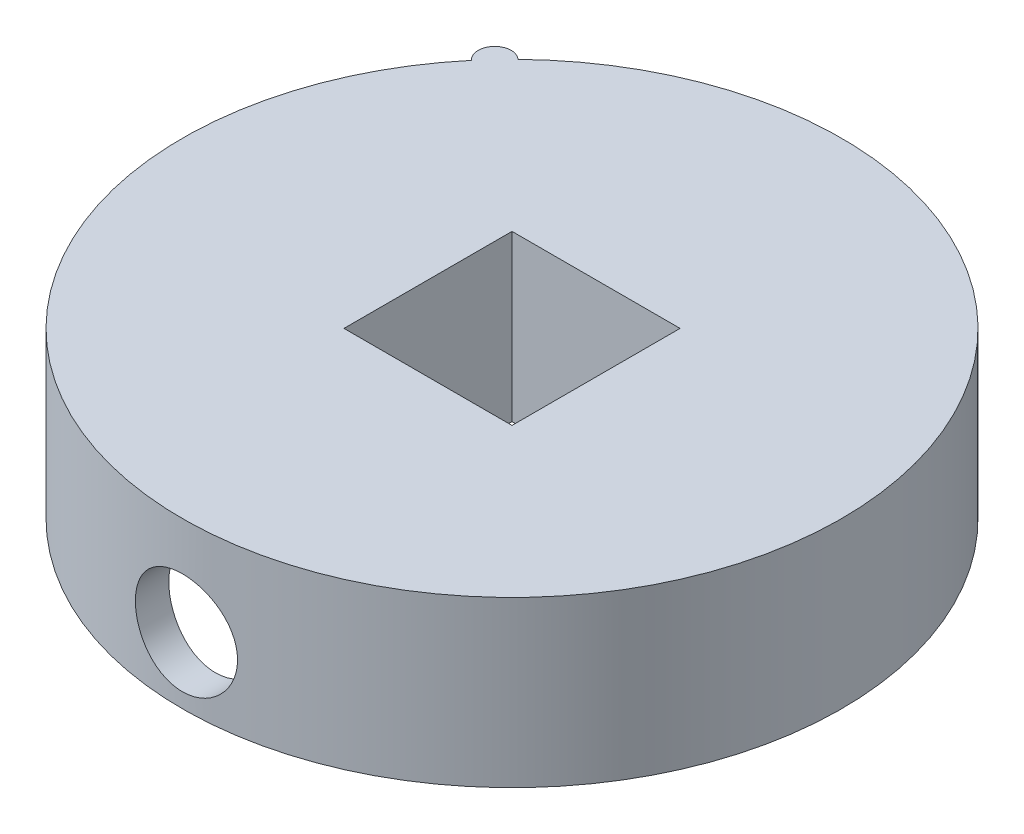
SolidWorks part; units mm, degrees
ref_plane "Спереди" through (0, 0, 0) normal (0, 0, 1) x (1, 0, 0)
ref_plane "Сверху" through (0, 0, 0) normal (0, 1, 0) x (1, 0, 0)
ref_plane "Справа" through (0, 0, 0) normal (1, 0, 0) x (0, 0, -1)
sketch "Sketch1" plane through (0, 0, 0) normal (0, 1, 0) x (1, 0, 0)
  circle A0 centre (0, 0) radius 20
  dimension "D1" = 40
extrude "Boss-Extrude1" add sketch "Sketch1" along normal blind 10
sketch "Sketch2" plane through (0, 0, 0) normal (0, -1, 0) x (1, 0, 0)
  line L1 (5.1, 5.1) -> (-5.1, 5.1)
  line L2 (5.1, 5.1) -> (5.1, -5.1)
  line L3 (5.1, -5.1) -> (-5.1, -5.1)
  line L4 (-5.1, 5.1) -> (-5.1, -5.1)
  line L5 (5.1, 5.1) -> (-5.1, -5.1) construction
  line L6 (5.1, -5.1) -> (-5.1, 5.1) construction
  point P0 (0, 0)
  dimension "D1" = 10.2
extrude "Cut-Extrude2" cut sketch "Sketch2" against normal through all
shell "Shell3" thickness 2 removed face at (0, 0, 0)
sketch "Sketch3" plane through (0, 0, 7.1) normal (0, 0, 1) x (1, 0, 0)
  line L0 (0, 8) -> (0, 0) construction
  line L1 (7.1, 8) -> (-7.1, 8) construction
  line L2 (7.1, 0) -> (-7.1, 0) construction
  circle A0 centre (0, 4) radius 3.1
  dimension "D1" = 6.2
extrude "Cut-Extrude3" cut sketch "Sketch3" along normal through all
sketch "Sketch4" plane through (0, 10, 0) normal (0, 1, 0) x (1, 0, 0)
  line L0 (0, 0) -> (-20, 0) construction
  line L1 (-20, 0) -> (-15.3209, 12.8558) construction
  line L2 (-15.3209, 12.8558) -> (0, 0) construction
  line L3 (-13.9603, 14.3216) -> (-15.3209, 12.8558)
  circle A0 centre (0, 0) radius 20 construction
  arc A1 (-15.3209, 12.8558) -> (-13.9603, 14.3216) centre (-14.6406, 13.5887) cw
  dimension "D2" = 1
  dimension "D1" = 40
  dimension "D3" = 2
extrude "Boss-Extrude2" add sketch "Sketch4" against normal up to surface (10 mm away) up to face at (0, 0, 18)
